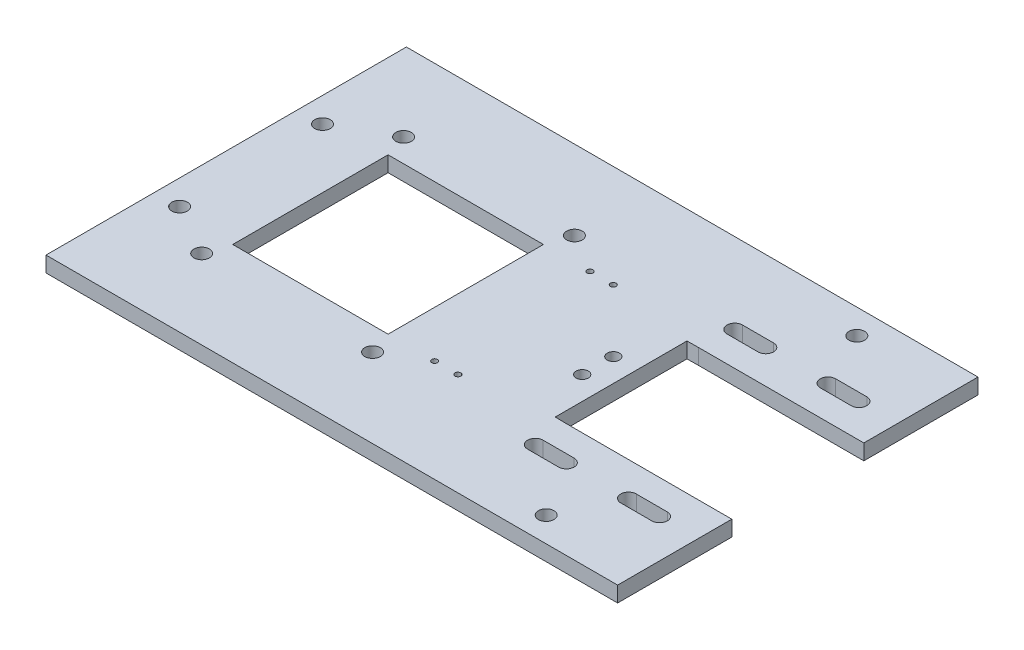
SolidWorks part; units mm, degrees
material "6061-T6 (SS)"
ref_plane "Front Plane" through (0, 0, 0) normal (0, 0, 1) x (1, 0, 0)
ref_plane "Top Plane" through (0, 0, 0) normal (0, 1, 0) x (1, 0, 0)
ref_plane "Right Plane" through (0, 0, 0) normal (1, 0, 0) x (0, 0, -1)
sketch "Sketch1" plane through (0, 0, 0) normal (0, 1, 0) x (1, 0, 0)
  line L0 (0, 0) -> (107.95, 0) construction
  line L1 (-107.95, -73.66) -> (107.95, -73.66)
  line L2 (-107.95, -73.66) -> (-107.95, 73.66) construction
  line L3 (-107.95, 73.66) -> (107.95, 73.66)
  line L4 (107.95, -73.66) -> (107.95, 73.66) construction
  line L5 (-107.95, -73.66) -> (107.95, 73.66) construction
  line L6 (-107.95, 73.66) -> (107.95, -73.66) construction
  line L7 (0, 0) -> (-107.95, 0) construction
  line L8 (107.95, 26.9875) -> (40.4625, 26.9875)
  line L9 (35.7, 26.924) -> (35.7, -26.924)
  line L10 (79.502, 37.592) -> (92.202, 37.592)
  line L11 (79.502, 43.942) -> (92.202, 43.942)
  line L12 (41.402, 37.592) -> (54.102, 37.592)
  line L13 (54.102, 43.942) -> (41.402, 43.942)
  line L14 (-107.95, -73.66) -> (-125.73, -73.66)
  line L15 (79.502, -43.942) -> (92.202, -43.942)
  line L16 (79.502, -37.592) -> (92.202, -37.592)
  line L17 (41.402, -37.592) -> (54.102, -37.592)
  line L18 (54.102, -43.942) -> (41.402, -43.942)
  line L19 (107.95, -26.9875) -> (40.4625, -26.9875)
  line L22 (40.4625, 26.9875) -> (-107.95, 26.9875) construction
  line L23 (-27.8, -31.75) -> (-27.8, 31.75)
  line L24 (-27.8, 31.75) -> (-91.3, 31.75)
  line L25 (-91.3, 31.75) -> (-91.3, -31.75)
  line L26 (-24.625, 41.275) -> (-24.625, 0) construction
  line L27 (-27.8, -31.75) -> (-91.3, -31.75)
  line L28 (107.95, -26.9875) -> (107.95, -73.66)
  line L29 (107.95, 73.66) -> (107.95, 26.9875)
  line L30 (-125.73, -73.66) -> (-125.73, 73.66)
  line L31 (-125.73, 73.66) -> (-107.95, 73.66)
  line L32 (35.7, 26.924) -> (40.4625, 26.9875)
  line L33 (35.7, -26.924) -> (40.4625, -26.9875)
  circle A0 centre (0.75, -31.75) radius 1.175
  arc A1 (92.202, 37.592) -> (92.202, 43.942) centre (92.202, 40.767) ccw
  arc A2 (79.502, 37.592) -> (79.502, 43.942) centre (79.502, 40.767) cw
  arc A3 (54.102, 43.942) -> (54.102, 37.592) centre (54.102, 40.767) cw
  arc A4 (41.402, 43.942) -> (41.402, 37.592) centre (41.402, 40.767) ccw
  circle A5 centre (26.175, 6.35) radius 2.4892
  arc A6 (79.502, -37.592) -> (79.502, -43.942) centre (79.502, -40.767) ccw
  arc A7 (92.202, -37.592) -> (92.202, -43.942) centre (92.202, -40.767) cw
  arc A8 (54.102, -43.942) -> (54.102, -37.592) centre (54.102, -40.767) ccw
  arc A9 (41.402, -43.942) -> (41.402, -37.592) centre (41.402, -40.767) cw
  circle A10 centre (26.175, -6.35) radius 2.4892
  circle A11 centre (-8.75, -31.75) radius 1.175
  circle A12 centre (-94.475, -41.275) radius 3.175
  circle A13 centre (-24.625, -41.275) radius 3.175
  circle A14 centre (-8.75, 31.75) radius 1.175
  circle A15 centre (-94.475, 41.275) radius 3.175
  circle A16 centre (-24.625, 41.275) radius 3.175
  circle A17 centre (0.75, 31.75) radius 1.175
  point P0 (0, 0)
  point P46 (35.7, 0)
  point P72 (-27.8, 0)
  point P73 (-91.3, 0)
  dimension "D5" = 3.175
  dimension "D6" = 40.767
  dimension "D8" = 6.35
  dimension "D11" = 9.525
  dimension "D12" = 2.35
  dimension "D15" = 69.85
  dimension "D16" = 4.7625
  dimension "D19" = 15.748
  dimension "D20" = 53.848
  dimension "D21" = 9.525
  dimension "D22" = 14.2875
  dimension "D13" = 9.5
  dimension "D25" = 0
  dimension "D27" = 6.35
  dimension "D28" = 6.35
  dimension "D1" = 147.32
  dimension "D2" = 215.9
  dimension "D3" = 26.9875
  dimension "D4" = 67.4875
  dimension "D7" = 12.7
  dimension "D9" = 25.4
  dimension "D10" = 12.7
  dimension "D14" = 63.5
  dimension "D17" = 3.175
  dimension "D18" = 17.78
  dimension "D23" = 72.25
  dimension "D24" = 19.05
  dimension "D26" = 63.5
extrude "Boss-Extrude1" add sketch "Sketch1" along normal blind 6.35
sketch "Sketch3" plane through (0, 6.35, 0) normal (0, 1, 0) x (1, 0, 0)
  line L0 (107.95, 73.66) -> (-125.73, 73.66) construction
  line L1 (-125.73, -73.66) -> (107.95, -73.66) construction
  line L2 (-125.73, 73.66) -> (-125.73, -73.66) construction
  line L3 (107.95, 26.9875) -> (107.95, 73.66) construction
  line L4 (107.95, -73.66) -> (107.95, -26.9875) construction
  circle A0 centre (-115.57, 29.21) radius 3.175
  circle A1 centre (-115.57, -29.21) radius 3.175
  circle A2 centre (68.58, 63.5) radius 3.175
  circle A3 centre (68.58, -63.5) radius 3.175
  dimension "D1" = 6.35
  dimension "D2" = 6.35
  dimension "D3" = 44.45
  dimension "D4" = 44.45
  dimension "D5" = 10.16
  dimension "D6" = 10.16
  dimension "D7" = 6.35
  dimension "D8" = 39.37
  dimension "D9" = 10.16
  dimension "D10" = 39.37
  dimension "D11" = 10.16
  dimension "D12" = 6.35
extrude "Cut-Extrude1" cut sketch "Sketch3" against normal up to surface (6.35 mm away) up to face at (-24.625, 0, -38.1)
